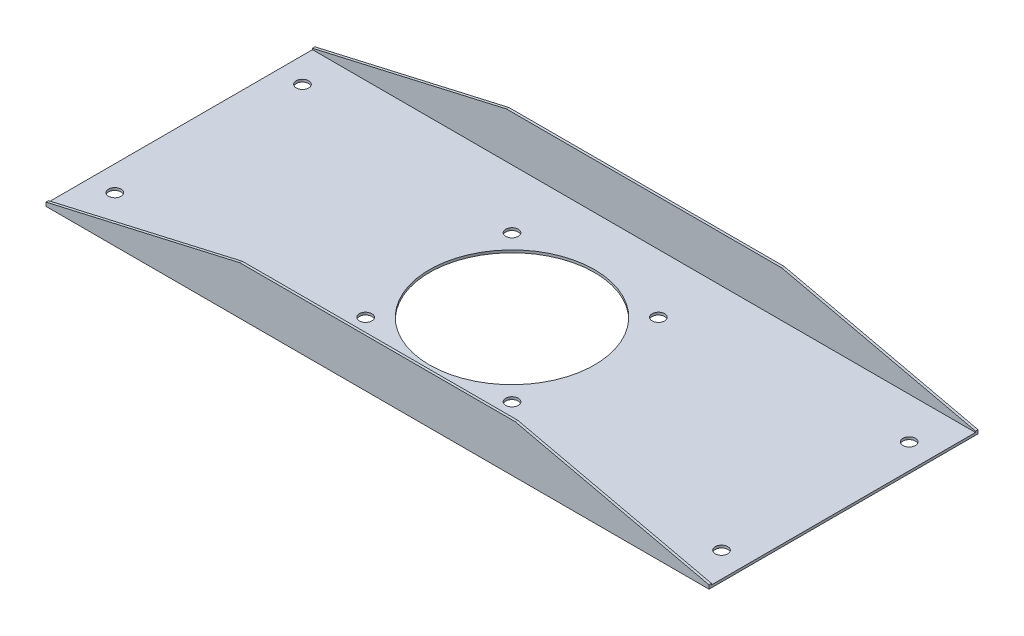
SolidWorks part; units mm, degrees
ref_plane "Спереди" through (0, 0, 0) normal (0, 0, 1) x (1, 0, 0)
ref_plane "Сверху" through (0, 0, 0) normal (0, 1, 0) x (1, 0, 0)
ref_plane "Справа" through (0, 0, 0) normal (1, 0, 0) x (0, 0, -1)
sketch "Эскиз1" plane through (0, 0, 0) normal (1, 0, 0) x (0, 0, -1)
  line L0 (-105, 0) -> (110, 0)
  line L1 (110, 0) -> (110, 38.5)
  line L2 (-105, 0) -> (-105, 38.5)
  dimension "D1" = 215
  dimension "D2" = 38.5
  dimension "D3" = 38.5
extrude "Вытянуть-Тонкостенный1" add sketch "Эскиз1" along normal blind 530 thin thin type one direction wall 2
sketch "Эскиз2" plane through (0, 0, -110) normal (0, 0, -1) x (-1, 0, 0)
  line L0 (-530, 0) -> (-530, 3)
  line L1 (-530, 38.5) -> (-530, 0) construction
  line L2 (-530, 3) -> (-375, 38.5)
  line L3 (-530, 38.5) -> (0, 38.5) construction
  line L4 (-375, 38.5) -> (-155, 38.5)
  line L5 (-155, 38.5) -> (0, 3)
  line L6 (0, 38.5) -> (0, 0) construction
  line L7 (0, 3) -> (0, 0)
  line L8 (0, 0) -> (-530, 0)
  dimension "D1" = 155
  dimension "D2" = 155
  dimension "D3" = 3
extrude "Вырез-Вытянуть2" cut sketch "Эскиз2" against normal through all flip side to cut
sketch "Эскиз3" plane through (0, 2, 0) normal (0, 1, 0) x (1, 0, 0)
  line L0 (20, 115.302) -> (20, -116.3672) construction
  line L1 (0, 108) -> (0, -103) construction
  line L2 (0, 110) -> (155, 110) construction
  line L3 (510, 126.018) -> (510, -161.4271) construction
  line L4 (530, 108) -> (530, -103) construction
  line L5 (0, 108) -> (530, -103) construction
  line L6 (530, 108) -> (0, -103) construction
  line L7 (193.3427, 74.1573) -> (265, 2.5) construction
  line L8 (265, 2.5) -> (336.6573, -69.1573) construction
  line L9 (336.6573, 74.1573) -> (193.3427, -69.1573) construction
  circle A0 centre (20, 80) radius 5
  circle A1 centre (20, -70) radius 5
  circle A2 centre (510, 75) radius 5
  circle A3 centre (510, -75) radius 5
  circle A4 centre (265, 2.5) radius 66
  circle A5 centre (323.514, 61.014) radius 5
  circle A6 centre (323.514, -56.014) radius 5
  circle A7 centre (206.486, -56.014) radius 5
  circle A8 centre (206.486, 61.014) radius 5
  point P43 (265, 2.5)
  dimension "D2" = 30
  dimension "D5" = 4
  dimension "D1" = 20
  dimension "D3" = 150
  dimension "D4" = 20
extrude "Вырез-Вытянуть3" cut sketch "Эскиз3" against normal through all
